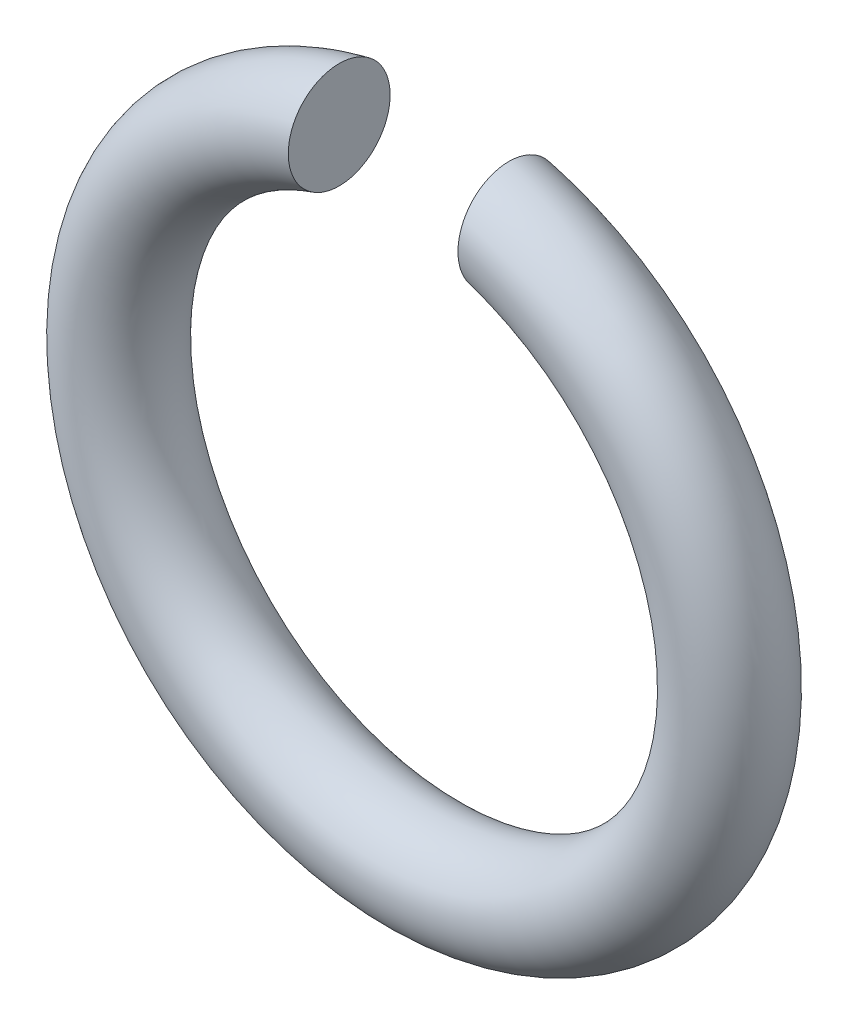
SolidWorks part; units mm, degrees
ref_plane "Front" through (0, 0, 0) normal (0, 0, 1) x (1, 0, 0)
ref_plane "Top" through (0, 0, 0) normal (0, 1, 0) x (1, 0, 0)
ref_plane "Right" through (0, 0, 0) normal (1, 0, 0) x (0, 0, -1)
sketch "Sketch1" plane through (0, 0, 0) normal (0, 0, 1) x (1, 0, 0)
  circle A1 centre (0, 0) radius 1.8
  dimension "D1" = 3.6
sketch "Sketch2" plane through (0, 0, 0) normal (0, 1, 0) x (1, 0, 0)
  circle A0 centre (1.8, 0) radius 0.3
  dimension "d1" = 0.6
sweep "Base-Sweep" add profiles "Sketch2" path "Sketch1"
sketch "Sketch3" plane through (0, 0, 0) normal (0, 0, 1) x (1, 0, 0)
  line L1 (-0.5, 0) -> (0.5, 0)
  line L2 (-0.5, 0) -> (-0.5, 2.1)
  line L3 (-0.5, 2.1) -> (0.5, 2.1)
  line L4 (0.5, 0) -> (0.5, 2.1)
  dimension "B/2" = 0.5
  dimension "D3" = 2.1
extrude "Cut-Extrude1" cut sketch "Sketch3" against normal through all and the other way through all
equation "\"B/2@Sketch3\" = \"B@Sketch3\" / 2"
